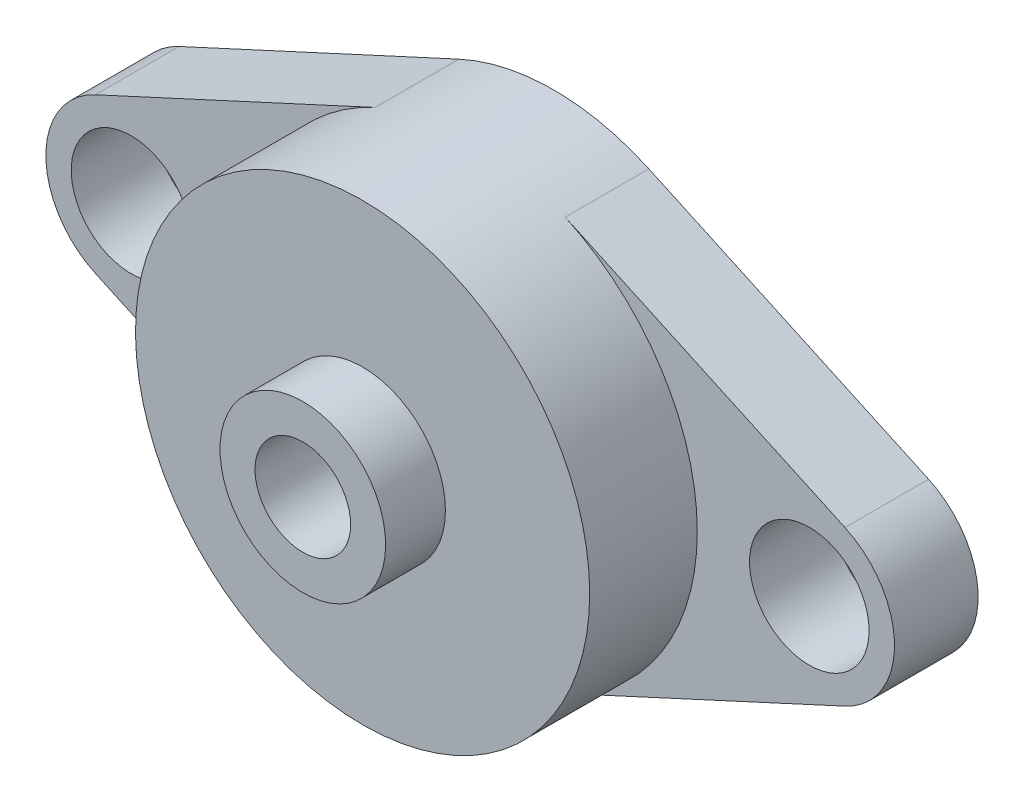
SolidWorks part; units mm, degrees
ref_plane "Front Plane" through (0, 0, 0) normal (0, 0, 1) x (1, 0, 0)
ref_plane "Top Plane" through (0, 0, 0) normal (0, 1, 0) x (1, 0, 0)
ref_plane "Right Plane" through (0, 0, 0) normal (1, 0, 0) x (0, 0, -1)
sketch "Sketch1" plane through (0, 0, 0) normal (0, 0, 1) x (1, 0, 0)
  line L0 (45.0453, 0) -> (-45.0453, 0) construction
  line L1 (56.3562, 0) -> (-56.3562, 0) construction
  line L2 (-49.779, 10.2728) -> (-12.6231, 27.3941)
  line L3 (-49.779, -10.2728) -> (-12.6231, -27.3941)
  line L4 (49.779, -10.2728) -> (12.6231, -27.3941)
  line L5 (12.6231, 27.3941) -> (49.779, 10.2728)
  circle A0 centre (0, 0) radius 6.35
  circle A1 centre (-45.0453, 0) radius 7.9375
  circle A2 centre (45.0453, 0) radius 7.9375
  arc A3 (12.6231, 27.3941) -> (-12.6231, 27.3941) centre (0, 0) ccw
  arc A4 (-12.6231, -27.3941) -> (12.6231, -27.3941) centre (0, 0) ccw
  arc A5 (-49.779, 10.2728) -> (-49.779, -10.2728) centre (-45.0453, 0) ccw
  arc A6 (49.779, 10.2728) -> (49.779, -10.2728) centre (45.0453, 0) cw
  point P5 (0, 0)
  point P13 (0, 0)
  point P18 (-56.3562, 0)
  point P19 (56.3562, 0)
  point P20 (0, 0)
  dimension "D1" = 12.7
  dimension "D2" = 15.875
  dimension "D3" = 15.875
  dimension "D4" = 30.1625
  dimension "D5" = 30.1625
  dimension "D6" = 90.0906
  dimension "D7" = 112.7125
extrude "Boss-Extrude1" add sketch "Sketch1" along normal mid plane 11.1125 contours A1 | A0 | A2 | L2 A3 L5 A6 L4 A4 L3 A5 region at (0, 0, 0) region at (-45.0453, 0, 0) region at (45.0453, 0, 0)
sketch "Sketch2" plane through (0, 0, 5.5562) normal (0, 0, 1) x (1, 0, 0)
  circle A0 centre (0, 0) radius 30.1625
  arc A1 (12.6231, 27.3941) -> (-12.6231, 27.3941) centre (0, 0) ccw construction
  arc A2 (12.6231, 27.3941) -> (-12.6231, 27.3941) centre (0, 0) ccw
  circle A3 centre (0, 0) radius 6.35 construction
  circle A4 centre (0, 0) radius 6.35
  circle M3 centre (0, 0) radius 6.35
extrude "Boss-Extrude2" add sketch "Sketch2" along normal blind 14.2875 contours M3 | A0 region at (0, 0, 5.5562)
sketch "Sketch3" plane through (0, 0, 19.8438) normal (0, 0, 1) x (1, 0, 0)
  circle A0 centre (0, 0) radius 11
  circle A1 centre (0, 0) radius 6.35 construction
  circle A2 centre (0, 0) radius 6.35
  circle M3 centre (0, 0) radius 6.35
  dimension "D1" = 22
extrude "Boss-Extrude3" add sketch "Sketch3" along normal blind 7.9375 contours M3 | A0 region at (0, 0, 19.8438)
